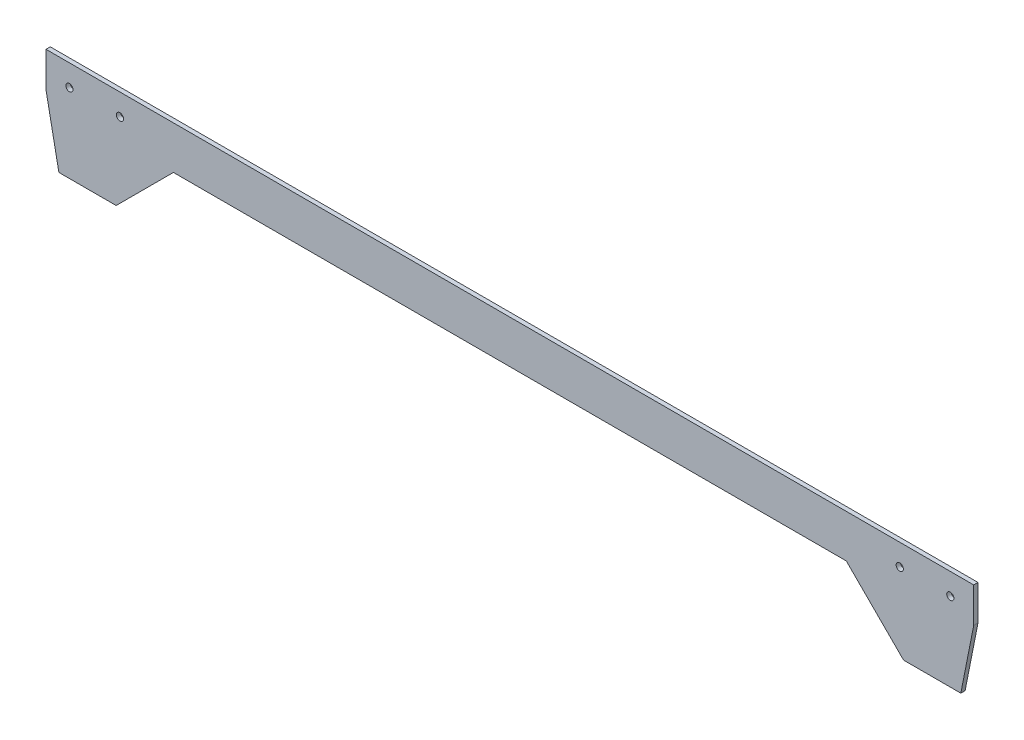
SolidWorks part; units mm, degrees
ref_plane "Alzado" through (0, 0, 0) normal (0, 0, 1) x (1, 0, 0)
ref_plane "Planta" through (0, 0, 0) normal (0, 1, 0) x (1, 0, 0)
ref_plane "Vista lateral" through (0, 0, 0) normal (1, 0, 0) x (0, 0, -1)
sketch "Croquis1" plane through (0, 0, 0) normal (0, 0, 1) x (1, 0, 0)
  line L0 (-600, -30) -> (-600, -110) construction
  line L1 (-600, -30) -> (-560, -30) construction
  line L2 (-600, -30) -> (-600, 30) construction
  line L3 (-600, 30) -> (600, 30)
  line L4 (600, -30) -> (600, 30) construction
  line L5 (-600, -30) -> (600, 30) construction
  line L6 (-600, 30) -> (600, -30) construction
  line L7 (600, -30) -> (560, -30) construction
  line L8 (600, -30) -> (600, 30) construction
  line L9 (600, 30) -> (560, 30)
  line L10 (560, -30) -> (560, 30) construction
  line L11 (-600, 30) -> (-560, 30)
  line L12 (-600, 30) -> (-600, -30) construction
  line L13 (-600, -30) -> (-560, -30) construction
  line L14 (-560, 30) -> (-560, -30) construction
  line L15 (-600, -110) -> (-550, -110)
  line L16 (-600, -110) -> (-630, -110)
  line L17 (-600, 0) -> (-638, 0) construction
  line L18 (-619, 0) -> (-619, 19) construction
  line L19 (-619, 0) -> (-619, -19) construction
  line L20 (-638, -19) -> (-600, -19) construction
  line L21 (-648, 30) -> (-648, -19)
  line L22 (-638, -19) -> (-638, 19) construction
  line L23 (-600, -19) -> (-600, 19)
  line L24 (-638, 19) -> (-600, 19) construction
  line L25 (-638, -19) -> (-600, 19) construction
  line L26 (-600, -19) -> (-638, 19) construction
  line L27 (-550, -110) -> (-470, -30)
  line L29 (-648, -19) -> (-630, -110)
  line L30 (550, -110) -> (470, -30)
  line L31 (-648, 30) -> (-600, 30)
  line L32 (-470, -30) -> (470, -30)
  line L33 (-560, -30) -> (-560, 30) construction
  line L34 (600, -110) -> (550, -110)
  line L35 (600, -110) -> (630, -110)
  line L36 (648, -19) -> (630, -110)
  line L37 (648, 30) -> (600, 30)
  line L38 (648, 30) -> (648, -19)
  line L39 (638, -19) -> (638, 19) construction
  line L40 (600, 0) -> (638, 0) construction
  line L41 (619, 0) -> (619, -19) construction
  line L42 (638, -19) -> (600, -19) construction
  line L43 (600, -19) -> (600, 19) construction
  line L44 (638, 19) -> (600, 19) construction
  line L45 (560, -30) -> (600, -30) construction
  line L46 (-600, 0) -> (-615.3, 0) construction
  line L47 (-580, -30) -> (-580, 30) construction
  line L48 (600, 30) -> (648, 30)
  circle A0 centre (-615.3, 0) radius 5
  circle A1 centre (-544.7, 0) radius 5
  circle A2 centre (544.7, 0) radius 5
  circle A3 centre (615.3, 0) radius 5
  point P0 (0, 0)
  dimension "D1" = 1200
  dimension "D2" = 60
  dimension "D3" = 40
  dimension "D4" = 40
  dimension "D5" = 50
  dimension "D6" = 30
  dimension "D7" = 38
  dimension "D8" = 38
  dimension "D9" = 135
  dimension "D10" = 49
  dimension "D11" = 113.1371
  dimension "D12" = 92.7631
  dimension "D13" = 15.3
extrude "Saliente-Extruir1" add sketch "Croquis1" along normal blind 6 contours L38 L37 L3 L31 L21 L29 L16 L15 L27 L32 L30 L34 L35 L36 A1 A0 A2 A3 region at (0, -13.5847, 0)
